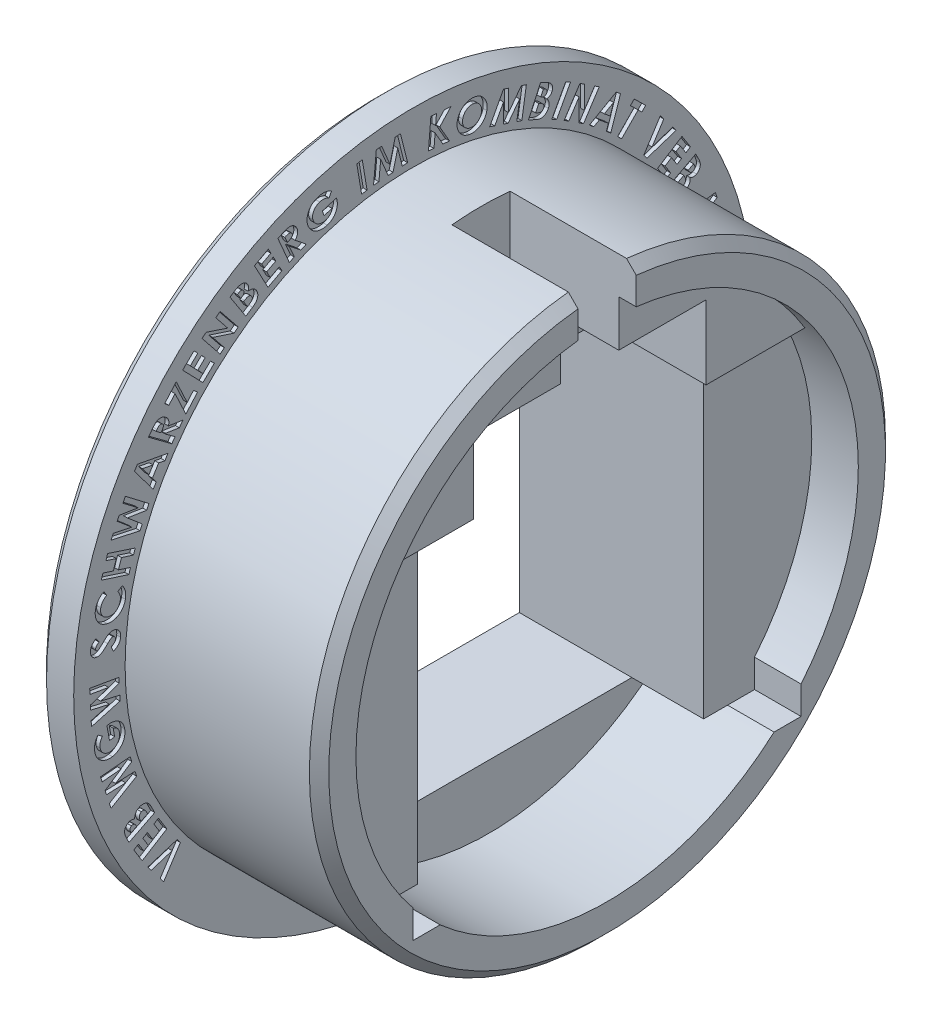
SolidWorks part; units mm, degrees
ref_plane "Ebene vorne" through (0, 0, 0) normal (0, 0, 1) x (1, 0, 0)
ref_plane "Ebene oben" through (0, 0, 0) normal (0, 1, 0) x (1, 0, 0)
ref_plane "Ebene rechts" through (0, 0, 0) normal (1, 0, 0) x (0, 0, -1)
sketch "Skizze1" plane through (0, 0, 0) normal (0, 1, 0) x (1, 0, 0)
  line L0 (-3.3698, 0) -> (19.5736, 0) construction
  line L1 (0, 0) -> (0, 17.5)
  line L2 (0, 17.5) -> (1.9, 17.5)
  line L3 (1.9, 17.5) -> (1.9, 14.85)
  line L4 (1.9, 14.85) -> (11.9, 14.85)
  line L7 (11.9, 14.85) -> (11.9, 12.95)
  line L8 (11.9, 12.95) -> (1.9, 12.95)
  line L9 (1.9, 12.95) -> (1.9, 0)
  line L10 (1.9, 0) -> (0, 0)
  dimension "D1" = 1.9
  dimension "D2" = 35
  dimension "D3" = 29.7
  dimension "D4" = 1.9
  dimension "D5" = 10
revolve "Rotation1" add sketch "Skizze1" angle 360 about L0
sketch "Skizze2" plane through (0, 0, 0) normal (-1, 0, 0) x (0, 0, 1)
  line L0 (0, 0) -> (0, -1.5) construction
  line L1 (-7.375, -9.675) -> (7.375, -9.675)
  line L2 (-7.375, -9.675) -> (-7.375, 6.675)
  line L3 (-7.375, 6.675) -> (7.375, 6.675)
  line L4 (7.375, -9.675) -> (7.375, 6.675)
  line L5 (-7.375, -9.675) -> (7.375, 6.675) construction
  line L6 (-7.375, 6.675) -> (7.375, -9.675) construction
  point P0 (0, -1.5)
  dimension "D1" = 16.35
  dimension "D2" = 14.75
  dimension "D3" = 1.5
extrude "Schnitt-Linear austragen1" cut sketch "Skizze2" against normal through all
sketch "Skizze3" plane through (1.9, 0, 0) normal (1, 0, 0) x (0, 0, -1)
  line L0 (-8.608, -9.675) -> (8.608, -9.675)
  circle A0 centre (0, 0) radius 12.95 construction
  circle A1 centre (0, 0) radius 12.95 construction
  arc A2 (-8.608, -9.675) -> (8.608, -9.675) centre (0, 0) ccw
extrude "Aufsatz-Linear austragen1" add sketch "Skizze3" along normal blind 3.9
sketch "Skizze4" plane through (1.9, 0, 0) normal (1, 0, 0) x (0, 0, -1)
  line L0 (-11.0972, 6.675) -> (11.0972, 6.675)
  arc A0 (8.608, -9.675) -> (-8.608, -9.675) centre (0, 0) ccw construction
  arc A1 (11.0972, 6.675) -> (-11.0972, 6.675) centre (0, 0) ccw
extrude "Aufsatz-Linear austragen2" add sketch "Skizze4" along normal blind 9.1
sketch "Skizze6" plane through (0, 0, 0) normal (0, 0, 1) x (1, 0, 0)
  line L0 (5.4, 6.675) -> (5.4, 11.475)
  line L1 (11, 6.675) -> (1.9, 6.675) construction
  line L2 (5.4, 11.475) -> (8.4, 11.475)
  line L3 (8.4, 11.475) -> (8.4, 10.475)
  line L4 (8.4, 10.475) -> (11, 10.475)
  line L6 (11, 10.475) -> (11, 6.675)
  line L7 (11, 6.675) -> (5.4, 6.675)
  line L8 (0, 17.5) -> (0, -17.5) construction
  dimension "D1" = 5.4
  dimension "D2" = 3
  dimension "D3" = 4.8
  dimension "D4" = 3.8
extrude "Schnitt-Linear austragen2" cut sketch "Skizze6" against normal mid plane 12
sketch "Skizze7" plane through (1.9, 0, 0) normal (1, 0, 0) x (0, 0, -1)
  line L2 (-11.0972, 6.675) -> (-7.375, 6.675) construction
  line L3 (-7.375, -9.675) -> (-7.375, 6.675) construction
  line L5 (7.375, 6.675) -> (11.0972, 6.675) construction
  line L6 (-11.0972, 6.675) -> (-7.375, 6.675)
  line L7 (-7.375, -9.675) -> (-7.375, 6.675)
  line L8 (-7.375, -9.675) -> (-8.608, -9.675) construction
  line L9 (8.608, -9.675) -> (7.375, -9.675) construction
  line L10 (7.375, 6.675) -> (7.375, -9.675) construction
  line L11 (7.375, 6.675) -> (7.375, -9.675)
  line L12 (8.608, -9.675) -> (7.375, -9.675)
  line L13 (-7.375, -9.675) -> (-8.608, -9.675)
  line L14 (7.375, 6.675) -> (11.0972, 6.675)
  arc A1 (-11.0972, 6.675) -> (-8.608, -9.675) centre (0, 0) ccw construction
  arc A3 (-11.0972, 6.675) -> (-8.608, -9.675) centre (0, 0) ccw
  arc A4 (8.608, -9.675) -> (11.0972, 6.675) centre (0, 0) ccw construction
  arc A5 (8.608, -9.675) -> (11.0972, 6.675) centre (0, 0) ccw
extrude "Aufsatz-Linear austragen3" add sketch "Skizze7" along normal blind 7.6
chamfer "Fase1" distance 0.5 angle 45 2 edges at (0, 0, 17.5) (11.9, 0, 14.85)
sketch "Skizze8" plane through (0, 0, 0) normal (-1, 0, 0) x (0, 0, 1)
  line L0 (-7.375, 6.675) -> (-7.375, -9.675) construction
  line L1 (7.375, 6.675) -> (-7.375, 6.675) construction
  line L2 (-6.875, 8.175) -> (-6.875, 9.175) construction
  text T0 "LAN" font "Century Gothic" height 5
  dimension "D1" = 0.5
  dimension "D2" = 2.5
  dimension "D3" = 1.5
extrude "Schnitt-Linear austragen3" cut sketch "Skizze8" against normal blind 0.4
sketch "Skizze10" plane through (11.9, 0, 0) normal (1, 0, 0) x (0, 0, -1)
  line L0 (-1.5, 10.475) -> (-1.5, 14.774)
  line L1 (6, 10.475) -> (-6, 10.475) construction
  line L2 (-1.5, 10.475) -> (1.5, 10.475)
  line L3 (1.5, 10.475) -> (1.5, 14.774)
  circle A0 centre (0, 0) radius 14.85 construction
  arc A1 (1.5, 14.774) -> (-1.5, 14.774) centre (0, 0) ccw
  point P6 (0, 10.475)
  dimension "D1" = 3
extrude "Schnitt-Linear austragen4" cut sketch "Skizze10" against normal up to surface (6.5 mm away) up to face at (5.4, 9.075, 0)
sketch "Skizze12" plane through (1.9, 0, 0) normal (1, 0, 0) x (0, 0, -1)
  line L0 (0, 0) -> (-11.6439, -9.7704) construction
  line L1 (0, 0) -> (11.6439, -9.7704) construction
  line L2 (0, 0) -> (0, 15.2) construction
  arc A0 (-11.6439, -9.7704) -> (11.6439, -9.7704) centre (0, 0) cw
  dimension "D1" = 15.2
  dimension "D2" = 260
sketch "Skizze11" plane through (1.9, 0, 0) normal (1, 0, 0) x (0, 0, -1)
  text T0 "VEB WGW SCHWARZENBERG IM KOMBINAT VEB MONSATOR " font "Century Gothic" height 1.5
extrude "Schnitt-Linear austragen5" cut sketch "Skizze11" against normal blind 0.2
sketch "Skizze13" plane through (11.9, 0, 0) normal (1, 0, 0) x (0, 0, -1)
  line L0 (10, -9.675) -> (-10, -9.675)
  line L1 (7.375, -9.675) -> (-7.375, -9.675) construction
  line L2 (0, 0) -> (0, -9.675) construction
  line L3 (-10, -9.675) -> (-10, -8.2282)
  line L4 (-10, -8.2282) -> (10, -8.2282)
  line L5 (10, -8.2282) -> (10, -9.675)
  arc A0 (-11.0972, 6.675) -> (-8.608, -9.675) centre (0, 0) ccw construction
  arc A1 (8.608, -9.675) -> (11.0972, 6.675) centre (0, 0) ccw construction
  point P7 (0, 0)
  point P13 (0, 0)
  point P14 (0, 0)
  dimension "D1" = 20
extrude "Schnitt-Linear austragen6" cut sketch "Skizze13" against normal up to surface (2.4 mm away) up to face at (9.5, -1.6123, -9.3513)
